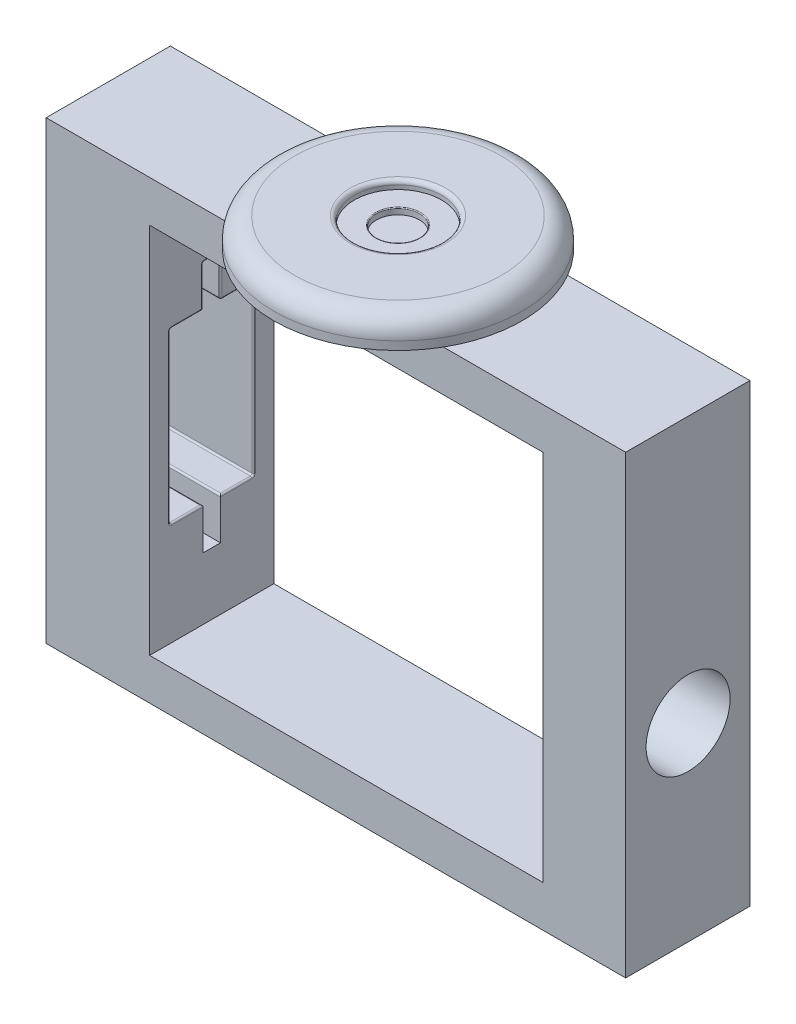
SolidWorks part; units mm, degrees
ref_plane "Front Plane" through (0, 0, 0) normal (0, 0, 1) x (1, 0, 0)
ref_plane "Top Plane" through (0, 0, 0) normal (0, 1, 0) x (1, 0, 0)
ref_plane "Right Plane" through (0, 0, 0) normal (1, 0, 0) x (0, 0, -1)
sketch "Sketch1" plane through (0, 0, 0) normal (1, 0, 0) x (0, 0, -1)
  line L2 (0, 0) -> (-30, 0)
  line L3 (-10.55, 7) -> (-10.55, 5)
  line L4 (-10.55, 5) -> (0, 5)
  line L5 (0, 5) -> (0, 0)
  line L6 (-10.55, 7) -> (-20.1025, 7)
  line L7 (-30, 0) -> (-30, 7)
  line L8 (-30, 7) -> (-20.1025, 7)
  dimension "D3" = 10.55
  dimension "D1" = 2
  dimension "D2" = 5
  dimension "D4" = 30
revolve "Revolve1" add sketch "Sketch1" angle 360 about L5
fillet "Fillet1" radius 1 1 edges at (0, 7, 10.55)
sketch "Sketch2" plane through (0, 5, 0) normal (0, 1, 0) x (1, 0, 0)
  circle A0 centre (0, 0) radius 5.2
  dimension "D1" = 10.4
extrude "Cut-Extrude1" cut sketch "Sketch2" against normal blind 1.5
fillet "Fillet2" radius 0.2 1 edges at (0, 5, 5.2)
fillet "Fillet3" radius 5 1 edges at (0, 7, 30)
ref_plane "Plane1" through (0, 0, 0) normal (0, -1, 0) x (-1, 0, 0)
sketch "Sketch4" plane through (0, 0, 0) normal (0, -1, 0) x (1, 0, 0)
  text T0 "1"
  text T1 "2"
  text T2 "3"
  text T3 "4"
extrude "Cut-Extrude2" cut sketch "Sketch4" against normal blind 1
sketch "Sketch5" plane through (0, 0, 0) normal (0, -1, 0) x (1, 0, 0)
  line L0 (0, -30) -> (0, 30)
  line L1 (-30, 0) -> (30, 0)
  circle A0 centre (0, 0) radius 30 construction
sketch "Sketch14" plane through (0, 0, 0) normal (0, -1, 0) x (1, 0, 0)
  line L0 (0, -30) -> (0, 30) construction
  line L1 (-70, -15) -> (70, -15)
  line L2 (-70, -15) -> (-70, 15)
  line L3 (-70, 15) -> (70, 15)
  line L4 (70, -15) -> (70, 15)
  line L5 (-70, -15) -> (70, 15) construction
  line L6 (-70, 15) -> (70, -15) construction
  point P0 (0, 0)
  dimension "D1" = 140
  dimension "D2" = 30
extrude "Boss-Extrude1" add sketch "Sketch14" along normal blind 10
sketch "Sketch15" plane through (0, -10, 0) normal (0, -1, 0) x (1, 0, 0)
  line L0 (70, 15) -> (-70, 15) construction
  line L1 (-70, -15) -> (-45, -15)
  line L2 (-70, -15) -> (-70, 15)
  line L3 (-70, 15) -> (-45, 15)
  line L4 (-45, -15) -> (-45, 15)
  line L6 (70, -15) -> (50, -15)
  line L7 (70, -15) -> (70, 15)
  line L8 (70, 15) -> (50, 15)
  line L9 (50, -15) -> (50, 15)
  dimension "D1" = 25
  dimension "D2" = 20
extrude "Boss-Extrude2" add sketch "Sketch15" along normal blind 90
sketch "Sketch16" plane through (0, -100, 0) normal (0, -1, 0) x (1, 0, 0)
  line L1 (-70, -15) -> (70, -15)
  line L2 (-70, -15) -> (-70, 15)
  line L3 (-70, 15) -> (70, 15)
  line L4 (70, -15) -> (70, 15)
extrude "Boss-Extrude3" add sketch "Sketch16" along normal blind 10
sketch "Sketch17" plane through (-45, 0, 0) normal (1, 0, 0) x (0, 0, -1)
  line L0 (-15, -110) -> (-15, 0) construction
  line L1 (-10.1, -34.2) -> (10.1, -34.2)
  line L2 (-10.1, -34.2) -> (-10.1, -75)
  line L3 (-10.1, -75) -> (10.1, -75)
  line L4 (10.1, -34.2) -> (10.1, -75)
  line L7 (15, -110) -> (-15, -110) construction
  dimension "D1" = 4.9
  dimension "D2" = 20.2
  dimension "D3" = 40.8
  dimension "D4" = 35
extrude "Cut-Extrude3" cut sketch "Sketch17" against normal blind 25
sketch "Sketch19" plane through (0, -34.2, 0) normal (0, -1, 0) x (1, 0, 0)
  line L0 (-45, 10.1) -> (-45, -10.1) construction
  line L1 (-45, -2.1) -> (-70, -2.1)
  line L2 (-45, -2.1) -> (-45, 2.1)
  line L3 (-45, 2.1) -> (-70, 2.1)
  line L4 (-70, -2.1) -> (-70, 2.1)
  line L5 (-70, 15) -> (-70, -15) construction
  line L6 (-70, -10.1) -> (-45, -10.1) construction
  line L7 (-70, 10.1) -> (-45, 10.1) construction
  dimension "D1" = 8
  dimension "D2" = 8
extrude "Cut-Extrude4" cut sketch "Sketch19" against normal blind 10
sketch "Sketch21" plane through (0, -75, 0) normal (0, 1, 0) x (1, 0, 0)
  line L0 (-45, -10.1) -> (-45, 10.1) construction
  line L1 (-45, 2.1) -> (-70, 2.1)
  line L2 (-45, 2.1) -> (-45, -2.1)
  line L3 (-45, -2.1) -> (-70, -2.1)
  line L4 (-70, 2.1) -> (-70, -2.1)
  line L5 (-70, 10.1) -> (-45, 10.1) construction
  line L6 (-70, -10.1) -> (-45, -10.1) construction
  dimension "D1" = 8
  dimension "D2" = 8
  dimension "D3" = 25
extrude "Cut-Extrude6" cut sketch "Sketch21" against normal blind 10
fillet "Fillet4" radius 0.4 28 edges at (-70, -75, -6.1) (-45, -75, -6.1) (-70, -34.2, -6.1) (-45, -34.2, -6.1) (-70, -24.2, 0) (-45, -24.2, 0) (-70, -34.2, 6.1) (-45, -34.2, 6.1) (-70, -75, 6.1) (-45, -75, 6.1) (-57.5, -75, -10.1) (-70, -54.6, -10.1) (-57.5, -34.2, -10.1) (-45, -54.6, -10.1) (-45, -29.2, 2.1) (-57.5, -24.2, 2.1) (-70, -29.2, 2.1) (-57.5, -34.2, 2.1) (-70, -29.2, -2.1) (-57.5, -24.2, -2.1) (-45, -29.2, -2.1) (-57.5, -34.2, -2.1) (-57.5, -34.2, 10.1) (-70, -54.6, 10.1) (-57.5, -75, 10.1) (-45, -54.6, 10.1) (-57.5, -75, 2.1) (-57.5, -75, -2.1)
sketch "Sketch22" plane through (70, 0, 0) normal (1, 0, 0) x (0, 0, -1)
  circle A0 centre (0.0887, -64.1926) radius 10.15
  dimension "D1" = 20.3
extrude "Cut-Extrude7" cut sketch "Sketch22" against normal blind 22
